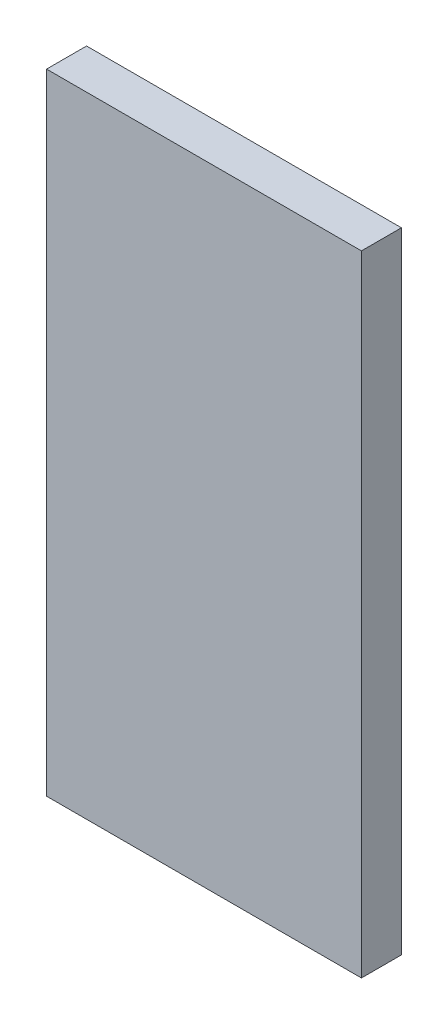
SolidWorks part; units mm, degrees
ref_plane "Front Plane" through (0, 0, 0) normal (0, 0, 1) x (1, 0, 0)
ref_plane "Top Plane" through (0, 0, 0) normal (0, 1, 0) x (1, 0, 0)
ref_plane "Right Plane" through (0, 0, 0) normal (1, 0, 0) x (0, 0, -1)
sketch "Sketch1" plane through (0, 0, 0) normal (0, 0, 1) x (1, 0, 0)
  line L1 (0, 0) -> (100, 0)
  line L2 (0, 0) -> (0, 200)
  line L3 (0, 200) -> (100, 200)
  line L4 (100, 0) -> (100, 200)
  dimension "D1" = 100
  dimension "D2" = 200
extrude "Boss-Extrude1" add sketch "Sketch1" along normal blind 12.7
equation "\"Plate_Height\"= 0.2m"
equation "\"Plate_Width\"= 0.1m"
equation "\"Plate_Thickness\"= 0.00635 * 2m"
